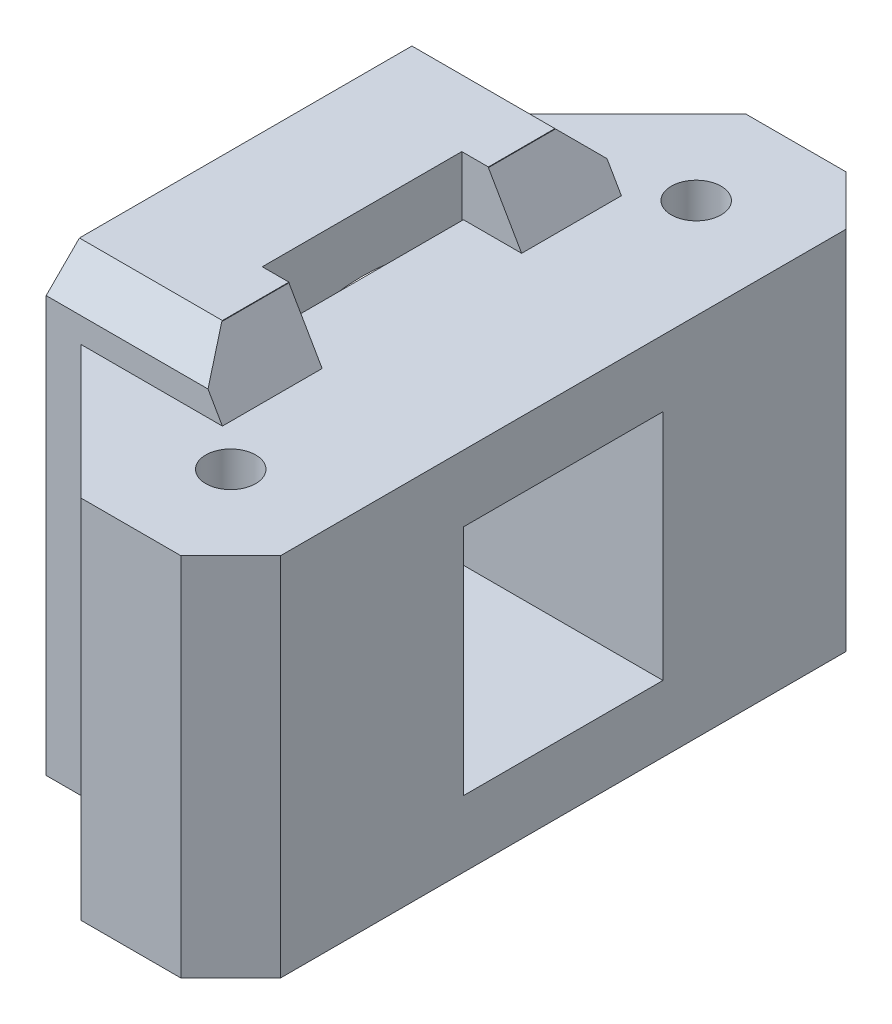
SolidWorks part; units mm, degrees
ref_plane "Front Plane" through (0, 0, 0) normal (0, 0, 1) x (1, 0, 0)
ref_plane "Top Plane" through (0, 0, 0) normal (0, 1, 0) x (1, 0, 0)
ref_plane "Right Plane" through (0, 0, 0) normal (1, 0, 0) x (0, 0, -1)
sketch "Sketch1" plane through (0, 0, 0) normal (0, 1, 0) x (1, 0, 0)
  line L0 (-6, 17) -> (-3, 20)
  line L1 (-3, 20) -> (3, 20)
  line L2 (-6, 17) -> (-6, -17)
  line L3 (-3, -20) -> (3, -20)
  line L4 (6, 17) -> (6, -17)
  line L5 (-6, 20) -> (6, -20) construction
  line L6 (-6, -20) -> (6, 20) construction
  line L7 (3, 20) -> (6, 17)
  line L8 (-6, -17) -> (-3, -20)
  line L9 (3, -20) -> (6, -17)
  circle A0 centre (0, 14) radius 1.5
  circle A1 centre (0, -14) radius 1.5
  point P0 (0, 0)
  dimension "D3" = 3
  dimension "D1" = 40
  dimension "D2" = 12
  dimension "D4" = 28
  dimension "D9" = 14
extrude "Boss-Extrude1" add sketch "Sketch1" along normal blind 3 contours A0 | L2 L8 L3 L9 L4 L7 L1 L0 | A1
sketch "Sketch2" plane through (0, 3, 0) normal (0, 1, 0) x (1, 0, 0)
  line L0 (-6, 17) -> (-6, -17) construction
  line L1 (-6.1, 12) -> (-4.5, 12)
  line L2 (-6.1, 12) -> (-6.1, 6)
  line L3 (-6.1, 6) -> (-4.5, 6)
  line L4 (-4.5, 12) -> (-4.5, 6)
  line L5 (-3, -20) -> (3, -20) construction
  line L6 (-6.1, -6) -> (-4.5, -6)
  line L7 (-6.1, -6) -> (-6.1, -12)
  line L8 (-6.1, -12) -> (-4.5, -12)
  line L9 (-4.5, -6) -> (-4.5, -12)
  line L10 (-3, 20) -> (3, 20) construction
  point P4 (-5.3188, -12)
  point P5 (-5.1046, 6)
  dimension "D1" = 6
  dimension "D2" = 6
  dimension "D3" = 8
  dimension "D4" = 8
  dimension "D5" = 1.5
  dimension "D6" = 1.5
  dimension "D7" = 0.1
  dimension "D8" = 0.1
extrude "Boss-Extrude2" add sketch "Sketch2" against normal blind 29 from offset 22.5 contours L2 L1 L4 L3 | L9 L8 L7 L6
sketch "Sketch4" plane through (0, 3, 0) normal (0, 1, 0) x (1, 0, 0)
  line L12 (-3, 20) -> (-6, 17)
  line L13 (-6, 17) -> (-6, 12)
  line L14 (-4.5, 12) -> (-4.5, 6)
  line L15 (-4.5, 6) -> (-6, 6)
  line L16 (-4.5, -6) -> (-4.5, -12)
  line L17 (-6, -12) -> (-6, -17)
  line L18 (-6, -17) -> (-3, -20)
  line L19 (-3, -20) -> (3, -20)
  line L20 (3, -20) -> (6, -17)
  line L21 (6, -17) -> (6, 17)
  line L22 (6, 17) -> (3, 20)
  line L23 (3, 20) -> (-3, 20)
  line L24 (-3, 20) -> (-6, 17)
  line L25 (-6, 17) -> (-6, 12)
  line L26 (-4.5, 12) -> (-4.5, 6)
  line L28 (-4.5, -6) -> (-4.5, -12)
  line L29 (-6, -12) -> (-6, -17)
  line L30 (-6, -17) -> (-3, -20)
  line L31 (-3, -20) -> (3, -20)
  line L32 (3, -20) -> (6, -17)
  line L33 (6, -17) -> (6, 17)
  line L34 (6, 17) -> (3, 20)
  line L35 (3, 20) -> (-3, 20)
  line L40 (-4.5, 6) -> (-6, 6)
  line L41 (-6, 6) -> (-6, -6)
  line L42 (-6, 6) -> (-6, -6)
  line L43 (-6, -6) -> (-4.5, -6)
  line L44 (-6, -6) -> (-4.5, -6)
  line L45 (-4.5, -12) -> (-6, -12)
  line L46 (-4.5, -12) -> (-6, -12)
  line L47 (-6, 12) -> (-4.5, 12)
  line L48 (-6, 12) -> (-4.5, 12)
  circle A0 centre (0, 14) radius 1.5 construction
  circle A1 centre (0, 14) radius 1.5
  circle A2 centre (0, -14) radius 1.5 construction
  circle A3 centre (0, -14) radius 1.5
  dimension "D1" = 0
extrude "Boss-Extrude5" add sketch "Sketch4" along normal blind 1 contours L24 L25 L48 L26 L40 L42 L44 L28 L46 L29 L30 L31 L32 L33 L34 L35 | A3 | A1
chamfer "Chamfer2" distance 2 angle 60 2 edges at (-4.5, 0, -9) (-4.5, 0, 9)
sketch "Sketch3" plane through (-6.1, 0, 0) normal (-1, 0, 0) x (0, 0, 1)
  line L1 (-12, 25.5) -> (12, 25.5)
  line L2 (-12, 25.5) -> (-12, -3.5)
  line L3 (-12, -3.5) -> (12, -3.5)
  line L4 (12, 25.5) -> (12, -3.5)
  circle A0 centre (0, 11) radius 11
  point P9 (0, 25.5)
  point P11 (-12, 11)
  dimension "D1" = 22
extrude "Boss-Extrude4" add sketch "Sketch3" along normal blind 7
chamfer "Chamfer3" distance 2 angle 45 4 edges at (-8.8, -3.5, -12) (-8.8, 25.5, -12) (-8.8, 25.5, 12) (-8.8, -3.5, 12)
ref_plane "Plane1" through (0, 11, 0) normal (0, -1, 0) x (-1, 0, 0)
mirror "Mirror1" about plane through (0, 11, 0) normal (0, -1, 0) of "Boss-Extrude5", "Boss-Extrude1", "Chamfer2"
sketch "Sketch5" plane through (0, 4, 0) normal (0, 1, 0) x (1, 0, 0)
  line L0 (6, -6) -> (-6, -6)
  line L1 (6, -17) -> (6, 17) construction
  line L2 (6, -6) -> (6, -17)
  line L3 (6, -17) -> (3, -20)
  line L4 (3, -20) -> (-3, -20)
  line L5 (-3, -20) -> (-6, -17)
  line L6 (-6, -17) -> (-6, -6)
  line L7 (0, 0) -> (-6, 0) construction
  line L9 (-6, 17) -> (-6, 6)
  line L10 (-3, 20) -> (-6, 17)
  line L11 (3, 20) -> (-3, 20)
  line L12 (6, 17) -> (3, 20)
  line L13 (6, 6) -> (6, 17)
  line L14 (6, 6) -> (-6, 6)
  circle A0 centre (0, -14) radius 2
  circle A1 centre (0, 14) radius 2
  dimension "D1" = 4
extrude "Boss-Extrude6" add sketch "Sketch5" along normal up to surface (14 mm away)
chamfer "Chamfer5" distance 5 angle 45 2 edges at (-6, 11, 12) (-6, 11, -12)
